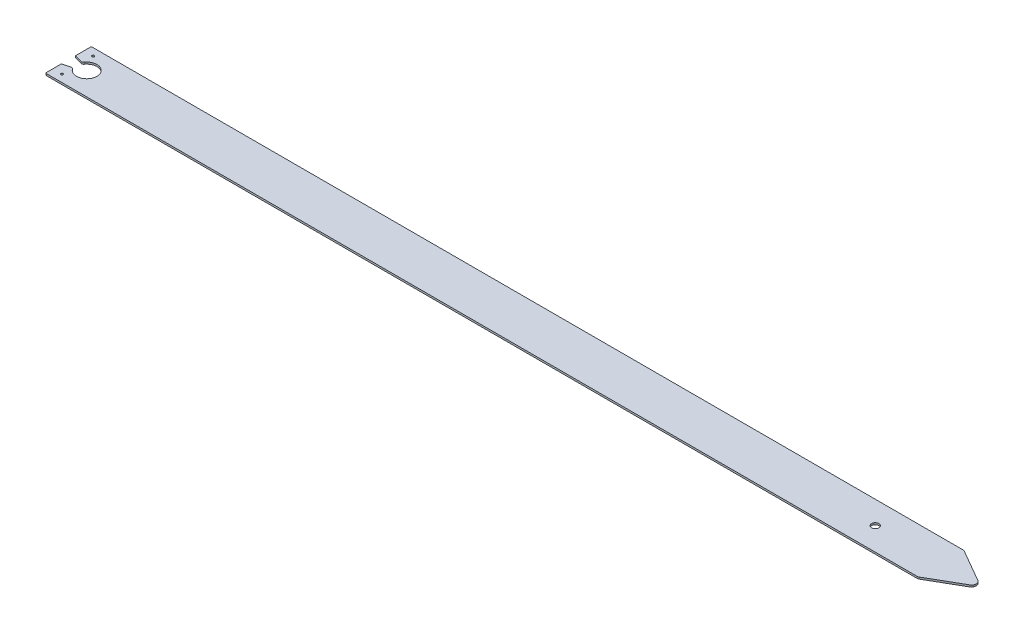
SolidWorks part; units mm, degrees
ref_plane "Front Plane" through (0, 0, 0) normal (0, 0, 1) x (1, 0, 0)
ref_plane "Top Plane" through (0, 0, 0) normal (0, 1, 0) x (1, 0, 0)
ref_plane "Right Plane" through (0, 0, 0) normal (1, 0, 0) x (0, 0, -1)
sketch "Sketch1" plane through (0, 0, 0) normal (0, 1, 0) x (1, 0, 0)
  line L0 (987.5, 29.3301) -> (952.859, 49.3301)
  line L1 (0, 0) -> (950.359, 0)
  line L2 (0, 0) -> (0, 50)
  line L3 (0, 50) -> (950.359, 50)
  line L5 (995, 25) -> (920.8862, 25) construction
  line L6 (987.5, 20.6699) -> (952.859, 0.6699)
  line L7 (987.5, 29.3301) -> (995, 25) construction
  line L8 (987.5, 20.6699) -> (995, 25) construction
  arc A0 (987.5, 29.3301) -> (987.5, 20.6699) centre (985, 25) cw
  arc A1 (952.859, 0.6699) -> (950.359, 0) centre (950.359, 5) cw
  arc A2 (952.859, 49.3301) -> (950.359, 50) centre (950.359, 45) ccw
  circle A3 centre (880, 25) radius 4
  circle A4 centre (10, 42) radius 1.25
  circle A5 centre (10, 8) radius 1.25
  point P12 (951.6987, 0)
  point P15 (951.6987, 50)
  dimension "D4" = 5
  dimension "D2" = 5
  dimension "D5" = 8
  dimension "D7" = 2.5
  dimension "D1" = 50
  dimension "D3" = 50
  dimension "D6" = 115
  dimension "D8" = 10
  dimension "D9" = 8
  dimension "D10" = 995
extrude "Boss-Extrude1" add sketch "Sketch1" along normal blind 2
ref_axis "Axis1" through (995, 2, -25) along (0, -1, 0)
fillet "Fillet1" radius 1 2 edges at (0, 1, -50) (0, 1, 0)
sketch "Sketch2" plane through (0, 2, 0) normal (0, 1, 0) x (1, 0, 0)
  line L0 (0, 25) -> (20, 25) construction
  line L1 (0, 49) -> (0, 1) construction
  line L2 (10, 25) -> (10, 20) construction
  line L3 (8.185, 19.5137) -> (0, 17.3205)
  line L4 (8.185, 30.4863) -> (0, 32.6795)
  line L5 (0, 32.6795) -> (0, 17.3205)
  arc A0 (10.8729, 18.5427) -> (10.8729, 31.4573) centre (20, 25) ccw
  arc A1 (10.8729, 18.5427) -> (8.185, 19.5137) centre (8.832, 17.0989) ccw
  arc A2 (8.185, 30.4863) -> (10.8729, 31.4573) centre (8.832, 32.9011) ccw
  point P14 (10, 30)
  dimension "D5" = 2.5
  dimension "D1" = 20
  dimension "D2" = 5
  dimension "D3" = 10
  dimension "D4" = 15
extrude "Cut-Extrude1" cut sketch "Sketch2" against normal up to surface (2 mm away) up to face at (578.561, 0, -25)
